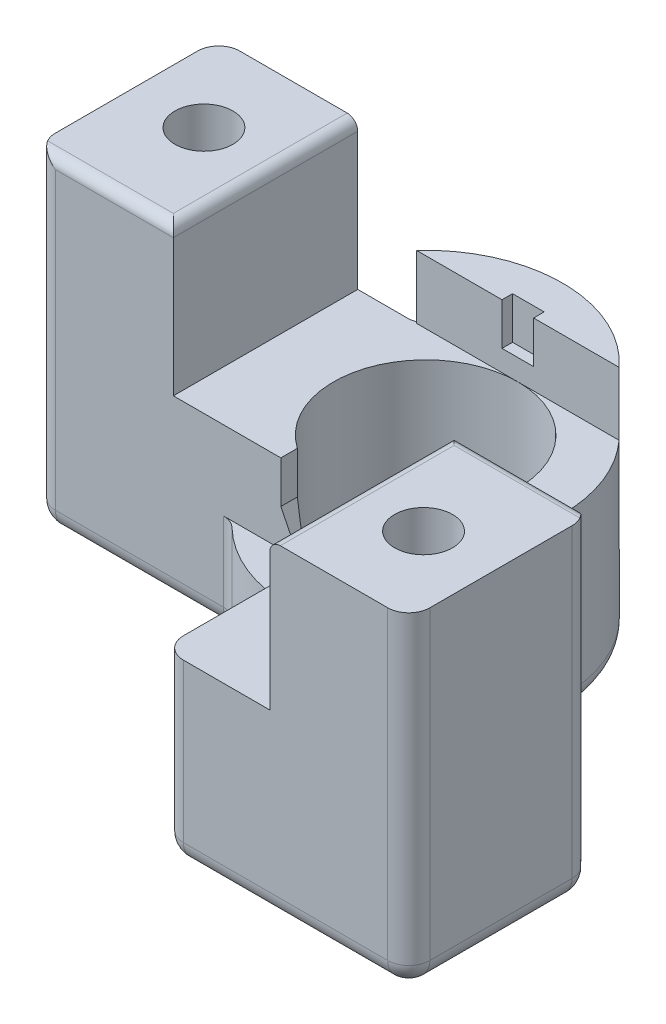
SolidWorks part; units mm, degrees
ref_plane "Front Plane" through (0, 0, 0) normal (0, 0, 1) x (1, 0, 0)
ref_plane "Top Plane" through (0, 0, 0) normal (0, 1, 0) x (1, 0, 0)
ref_plane "Right Plane" through (0, 0, 0) normal (1, 0, 0) x (0, 0, -1)
sketch "Sketch2" plane through (0, 0, 0) normal (0, 1, 0) x (1, 0, 0)
  circle A0 centre (0, 0) radius 11.1125
  circle A1 centre (0, 0) radius 16.51
  dimension "D1" = 33.02
  dimension "D2" = 22.225
extrude "Boss-Extrude1" add sketch "Sketch2" along normal blind 29.21
sketch "Sketch3" plane through (0, 29.21, 0) normal (0, 1, 0) x (1, 0, 0)
  line L0 (12.2103, 11.1125) -> (-12.2103, 11.1125)
  arc A2 (12.2103, 11.1125) -> (-12.2103, 11.1125) centre (0, 0) cw
  circle A3 centre (0, 0) radius 16.51 construction
  circle A4 centre (0, 0) radius 11.1125 construction
extrude "Cut-Extrude1" cut sketch "Sketch3" against normal offset from surface (7.62 mm away) 21.59 up to face at (0, 0, 16.51)
sketch "Sketch4" plane through (0, 0, 0) normal (0, 1, 0) x (1, 0, 0)
  line L0 (16.51, 0) -> (16.51, -38.1)
  line L1 (16.51, -38.1) -> (6.35, -38.1)
  line L2 (6.35, -38.1) -> (6.35, -15.24)
  line L3 (-20.5027, 16.51) -> (17.8921, 16.51) construction
  arc A0 (-12.2103, 11.1125) -> (12.2103, 11.1125) centre (0, 0) ccw construction
  arc A1 (12.2103, 11.1125) -> (-12.2103, 11.1125) centre (0, 0) ccw construction
  arc A2 (16.51, 0) -> (6.35, -15.24) centre (0, 0) cw
  dimension "D1" = 54.61
  dimension "D2" = 10.16
extrude "Boss-Extrude2" add sketch "Sketch4" along normal up to surface (21.59 mm away) up to face at (0, 21.59, 1.3494)
sketch "Sketch5" plane through (0, 0, 0) normal (0, 0, 1) x (1, 0, 0)
  line L0 (6.35, 21.59) -> (6.35, 16.51)
  line L1 (6.35, 21.59) -> (6.35, 0) construction
  line L2 (6.35, 16.51) -> (4.1275, 12.065)
  line L3 (4.1275, 12.065) -> (-4.1275, 12.065)
  line L4 (-4.1275, 12.065) -> (-6.35, 16.51)
  line L5 (-6.35, 16.51) -> (-6.35, 21.59)
  line L6 (6.35, 21.59) -> (-16.51, 21.59) construction
  line L7 (-6.35, 21.59) -> (6.35, 21.59)
  line L8 (-16.51, 0) -> (16.51, 0) construction
  point P12 (0, 12.065)
  dimension "D1" = 5.08
  dimension "D2" = 12.065
  dimension "D3" = 8.255
extrude "Cut-Extrude2" cut sketch "Sketch5" along normal through all
sketch "Sketch6" plane through (0, 0, 0) normal (0, 1, 0) x (1, 0, 0)
  line L0 (-12.2103, 11.1125) -> (-19.304, 11.1125)
  line L1 (-19.304, 11.1125) -> (-19.304, -11.1125)
  line L2 (-19.304, -11.1125) -> (-12.2103, -11.1125)
  line L3 (-6.35, -15.24) -> (-6.35, -9.1195) construction
  arc A0 (-12.2103, 11.1125) -> (-6.35, -15.24) centre (0, 0) ccw construction
  arc A1 (-12.2103, 11.1125) -> (-12.2103, -11.1125) centre (0, 0) ccw
  arc A2 (-4.1275, -10.3175) -> (4.1275, -10.3175) centre (0, 0) ccw construction
  dimension "D1" = 12.954
extrude "Boss-Extrude3" add sketch "Sketch6" along normal up to surface (21.59 mm away) up to face at (-9.7935, 21.59, 0.3309)
sketch "Sketch7" plane through (0, 29.21, 0) normal (0, 1, 0) x (1, 0, 0)
  line L0 (12.2103, 11.1125) -> (-12.2103, 11.1125) construction
  line L1 (-1.905, 11.1125) -> (1.905, 11.1125)
  line L2 (-1.905, 11.1125) -> (-1.905, 12.3825)
  line L3 (-1.905, 12.3825) -> (1.905, 12.3825)
  line L4 (1.905, 11.1125) -> (1.905, 12.3825)
  point P6 (0, 11.1125)
  dimension "D1" = 3.81
  dimension "D2" = 1.27
extrude "Cut-Extrude3" cut sketch "Sketch7" against normal offset from surface (5.08 mm away) 2.54 up to face at (-11.9118, 21.59, 1.6054)
sketch "Sketch8" plane through (0, 0, 38.1) normal (0, 0, 1) x (1, 0, 0)
  line L0 (16.51, 0) -> (16.51, 21.59)
  line L1 (16.51, 21.59) -> (19.304, 21.59)
  line L2 (19.304, 21.59) -> (19.304, 39.37)
  line L3 (19.304, 39.37) -> (36.068, 39.37)
  line L4 (36.068, 39.37) -> (36.068, 0)
  line L6 (6.35, 16.51) -> (6.35, 21.59) construction
  line L8 (16.51, 0) -> (36.068, 0)
  dimension "D1" = 12.954
  dimension "D2" = 17.78
  dimension "D3" = 16.764
extrude "Boss-Extrude4" add sketch "Sketch8" against normal blind 22.225
sketch "Sketch9" plane through (0, 0, 11.1125) normal (0, 0, 1) x (1, 0, 0)
  line L0 (-19.304, 0) -> (-19.304, 39.37)
  line L1 (-19.304, 39.37) -> (-36.068, 39.37)
  line L2 (-36.068, 39.37) -> (-36.068, 0)
  line L3 (-36.068, 0) -> (-19.304, 0)
  line L4 (36.068, 39.37) -> (19.304, 39.37) construction
extrude "Boss-Extrude5" add sketch "Sketch9" against normal up to surface (22.225 mm away) up to face at (-15.7572, 10.795, -11.1125)
sketch "Sketch10" plane through (0, 39.37, 0) normal (0, 1, 0) x (1, 0, 0)
  line L0 (-19.304, -11.1125) -> (-36.068, -11.1125) construction
  line L1 (-36.068, 11.1125) -> (-19.304, 11.1125) construction
  line L2 (36.068, -38.1) -> (19.304, -38.1) construction
  circle A0 centre (-27.686, 0.9525) radius 3.4925
  circle A1 centre (27.686, -27.94) radius 3.4925
  point P5 (-27.686, -11.1125)
  point P11 (27.686, -38.1)
  dimension "D2" = 6.985
  dimension "D4" = 6.985
  dimension "D1" = 10.16
  dimension "D3" = 10.16
extrude "Cut-Extrude4" cut sketch "Sketch10" against normal through all
sketch "Sketch12" plane through (0, 0, 0) normal (1, 0, 0) x (0, 0, -1)
  line L0 (-11.1125, 21.59) -> (-11.1125, 0) construction
  line L1 (-15.24, 21.59) -> (-15.24, 16.51) construction
  line L2 (-11.1125, 21.59) -> (-15.24, 21.59) construction
  line L3 (-11.1125, 21.59) -> (-11.1125, 12.065)
  line L4 (-15.24, 21.59) -> (-15.24, 16.51)
  line L5 (-11.1125, 21.59) -> (-15.24, 21.59)
  line L6 (-15.9857, 12.065) -> (-11.1125, 12.065)
  ellipse E0 centre (0, 3.81) end of major axis (0, -29.21) minor radius 16.51 (-15.24, 16.51) -> (-15.9857, 12.065) ccw construction
  ellipse E1 centre (0, 3.81) end of major axis (0, -29.21) minor radius 16.51 (-15.24, 16.51) -> (-15.9857, 12.065) ccw
extrude "Cut-Extrude5" cut sketch "Sketch12" against normal up to next
fillet "Fillet1" radius 2.54 10 edges at (16.51, 10.795, 15.875) (36.068, 19.685, 15.875) (36.068, 19.685, 38.1) (6.35, 10.795, 38.1) (6.35, 8.255, 15.24) (-12.2103, 6.0325, 11.1125) (-36.068, 19.685, 11.1125) (-36.068, 19.685, -11.1125) (-12.2103, 10.795, -11.1125) (0, 0, 11.1125)
fillet "Fillet2" radius 2.54 19 edges at (35.3241, 0, 16.6189) (26.289, 0, 15.875) (17.2539, 0, 15.1311) (16.51, 0, 6.6675) (6.4218, 0, -15.2099) (-12.3298, 0, -11.2993) (-23.4069, 0, -11.1125) (-35.3241, 0, -10.3686) (-36.068, 0, 0) (-35.3241, 0, 10.3686) (-23.4069, 0, 11.1125) (-12.3298, 0, 11.2993) (-4.6453, 0, 15.843) (5.4164, 0, 16.6976) (6.35, 0, 27.1126) (7.0939, 0, 37.3561) (21.209, 0, 38.1) (35.3241, 0, 37.3561) (36.068, 0, 26.9875)
fillet "Fillet3" radius 1.27 4 edges at (26.416, 39.37, 15.875) (-26.416, 39.37, 11.1125) (19.304, 39.37, 26.9875) (-19.304, 39.37, 0) tangent propagation no
sketch "Sketch13" plane through (0, 0, 0) normal (0, -1, 0) x (-1, 0, 0)
  line L0 (-17.018, -34.6075) -> (-17.018, -19.3675) construction
  line L1 (-9.3345, -34.925) -> (-9.3345, -9.525) construction
  line L2 (-36.068, -35.56) -> (-36.068, -18.415) construction
  line L3 (-8.89, -38.1) -> (-33.528, -38.1) construction
  line L4 (-6.35, -18.6651) -> (-6.35, -35.56) construction
  line L5 (18.288, -7.62) -> (18.288, 7.62) construction
  line L6 (23.749, -7.62) -> (23.749, 7.62) construction
  line L7 (36.068, 8.5725) -> (36.068, -8.5725) construction
  text T0 "MAIN" font "Century Gothic" height in points 16
  text T1 "BREAKER" font "Century Gothic" height in points 16
  text T2 "DNA" font "Century Gothic" height in points 16
  text T3 "4009" font "Century Gothic" height in points 16
  point P9 (-36.068, -26.9875)
  point P10 (-17.018, -26.9875)
  point P22 (36.068, 0)
  point P23 (18.288, 0)
  dimension "D1" = 25.4
  dimension "D2" = 15.24
  dimension "D3" = 19.05
  dimension "D4" = 3.175
  dimension "D5" = 2.9845
  dimension "D6" = 18.288
  dimension "D7" = 15.24
  dimension "D8" = 5.461
extrude "Cut-Extrude6" cut sketch "Sketch13" against normal blind 0.635
extrude "Boss-Extrude6" add sketch "Sketch13<2>" against normal up to surface (0.635 mm away) separate body up to face at (19.1338, 0.635, 21.2025)
sketch "Sketch13<2>" plane through (0, 0, 0) normal (0, -1, 0) x (-1, 0, 0) same geometry as "Sketch13"
